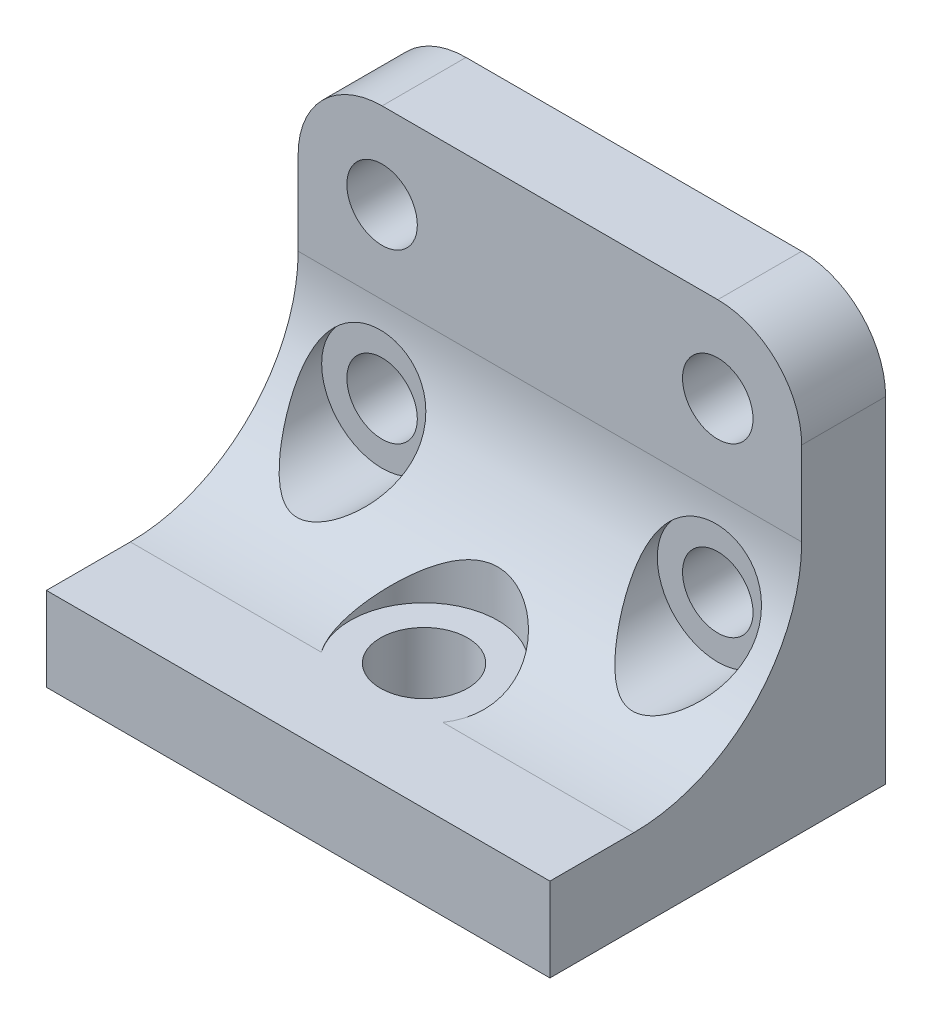
SolidWorks part; units mm, degrees
ref_plane "Front Plane" through (0, 0, 0) normal (0, 0, 1) x (1, 0, 0)
ref_plane "Top Plane" through (0, 0, 0) normal (0, 1, 0) x (1, 0, 0)
ref_plane "Right Plane" through (0, 0, 0) normal (1, 0, 0) x (0, 0, -1)
sketch "Sketch1" plane through (0, 0, 0) normal (0, 0, 1) x (1, 0, 0)
  line L0 (73.6349, -21) -> (73.6349, -20)
  line L1 (35.4859, -20) -> (110.55, -20) construction
  line L2 (110.55, -21) -> (38.1661, -21) construction
  line L3 (73.6349, -20) -> (103.6349, -20)
  line L4 (38.1661, -45) -> (110.55, -45) construction
  line L6 (73.6349, -21) -> (73.6349, -45)
  line L7 (73.6349, -45) -> (103.6349, -45)
  line L8 (103.6349, -45) -> (103.6349, -21)
  line L9 (103.6349, -20) -> (103.6349, -21)
  circle A4 centre (98.6349, -35.1) radius 2.1
  circle A5 centre (78.6349, -35.1) radius 2.1
  circle A6 centre (98.6349, -25.1) radius 2.1
  circle A7 centre (78.6349, -25.1) radius 2.1
  point P18 (88.6349, -21)
extrude "Boss-Extrude1" add sketch "Sketch1" along normal blind 5
sketch "Sketch3" plane through (0, 0, 5) normal (0, 0, 1) x (1, 0, 0)
  line L0 (103.6349, -45) -> (73.6349, -45)
  line L1 (103.6349, -45) -> (103.6349, -40)
  line L2 (73.6349, -45) -> (73.6349, -40)
  line L3 (103.6349, -40) -> (73.6349, -40)
extrude "Boss-Extrude2" add sketch "Sketch3" along normal blind 15
fillet "Fillet1" radius 5 2 edges at (73.6349, -20, 2.5) (103.6349, -20, 2.5)
sketch "Sketch2" plane through (0, 0, 5) normal (0, 0, 1) x (1, 0, 0)
  circle A0 centre (98.6349, -25.1) radius 3.6
  circle A1 centre (98.6349, -35.1) radius 3.6
  circle A2 centre (78.6349, -25.1) radius 3.6
  circle A3 centre (78.6349, -35.1) radius 3.6
sketch "Sketch4" plane through (0, -40, 0) normal (0, 1, 0) x (1, 0, 0)
  circle A0 centre (88.6349, -12.5) radius 2.6
extrude "Cut-Extrude2" cut sketch "Sketch4" against normal through all
fillet "Fillet2" radius 10 1 edges at (88.6349, -40, 5)
sketch "Sketch5" plane through (0, -40, 0) normal (0, 1, 0) x (1, 0, 0)
  circle A0 centre (88.6349, -12.5) radius 4.4
extrude "Cut-Extrude3" cut sketch "Sketch5" along normal through all
extrude "Cut-Extrude4" cut sketch "Sketch2" along normal through all
